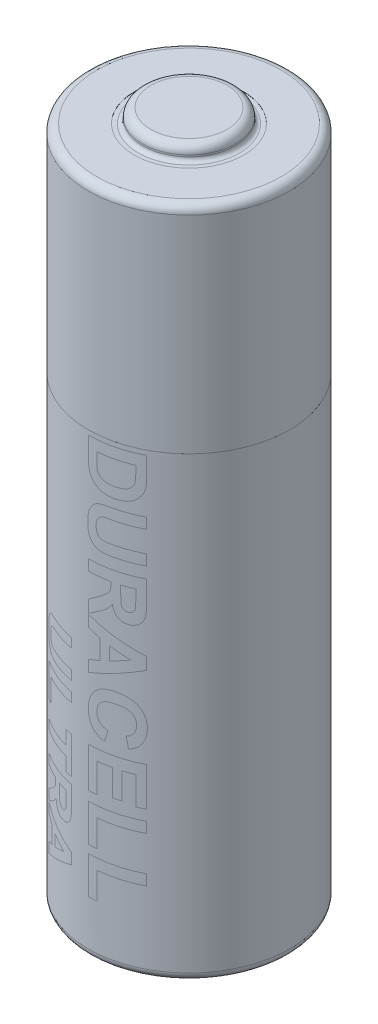
SolidWorks part; units mm, degrees
ref_plane "Front" through (0, 0, 0) normal (0, 0, 1) x (1, 0, 0)
ref_plane "Top" through (0, 0, 0) normal (0, 1, 0) x (1, 0, 0)
ref_plane "Right" through (0, 0, 0) normal (1, 0, 0) x (0, 0, -1)
sketch "Sketch1" plane through (0, 0, 0) normal (0, 0, 1) x (1, 0, 0)
  line L0 (0, 7.5818) -> (0, -7.5818) construction
  line L1 (0, 49.25) -> (0, -1)
  line L2 (3.95, 48.25) -> (3.95, 48.23)
  line L3 (6.65, 48.25) -> (3.95, 48.25)
  line L4 (7.25, 0.35) -> (7.25, 47.65)
  line L5 (0, 49.25) -> (2.75, 49.25)
  line L6 (6.2977, -0.25) -> (6.65, -0.25)
  line L7 (4.55, -0.24) -> (6.2977, -0.24)
  line L8 (3.35, 48.65) -> (3.35, 48.53)
  line L10 (3.65, 48.23) -> (3.95, 48.23)
  line L11 (0, -1) -> (3.95, -1)
  line L12 (4.25, -0.54) -> (4.25, -0.7)
  line L15 (6.2977, -0.24) -> (6.2977, -0.25)
  arc A0 (2.75, 49.25) -> (3.35, 48.65) centre (2.75, 48.65) cw
  arc A1 (3.95, -1) -> (4.25, -0.7) centre (3.95, -0.7) ccw
  arc A2 (6.65, 48.25) -> (7.25, 47.65) centre (6.65, 47.65) cw
  arc A3 (6.65, -0.25) -> (7.25, 0.35) centre (6.65, 0.35) ccw
  arc A4 (3.65, 48.23) -> (3.35, 48.53) centre (3.65, 48.53) cw
  arc A5 (4.25, -0.54) -> (4.55, -0.24) centre (4.55, -0.54) cw
  point P5 (3.35, 49.25)
  point P11 (4.25, -1)
  point P15 (7.25, 48.25)
  point P21 (7.25, -0.25)
  point P25 (3.35, 48.25)
  point P28 (4.25, -0.25)
  dimension "D1" = 0.6
  dimension "D8" = 0.3
  dimension "D9" = 0.6
  dimension "D10" = 0.3
  dimension "D11" = 0.3
  dimension "D2" = 7.25
  dimension "D3" = 48.5
  dimension "D4" = 0.75
  dimension "D5" = 1
  dimension "D6" = 2.75
  dimension "D7" = 4.25
revolve "Revolve1" add sketch "Sketch1" angle 360 about L0
ref_plane "Plane1" through (0, 0.35, 0) normal (0, -1, 0) x (1, 0, 0)
sketch "Sketch4" plane through (0, 0.35, 0) normal (0, -1, 0) x (1, 0, 0)
  circle A2 centre (0, 0) radius 7.2505
  circle A4 centre (0, 0) radius 6.2977
  dimension "D1" = 12.5954
  dimension "D2" = 14.501
extrude "Extrude3" add sketch "Sketch4" against normal blind 32.4
ref_plane "Plane2" through (0, 0, 7.25) normal (0, 0, 1) x (1, 0, 0)
sketch "Sketch5" plane through (0, 0, 7.25) normal (0, 0, 1) x (1, 0, 0)
  line L0 (0, 0) -> (0, 32.8291) construction
  text T0 "<b>DURACELL</b>" font "Arial" height 3.5
wrap "DURACELL" sketch "Sketch5" wrap type scribe source sketch "Sketch5" face at (0, 32.75, -7.2505)
sketch "Sketch6" plane through (0, 0, 7.25) normal (0, 0, 1) x (1, 0, 0)
  line L0 (-4.4268, 3.7211) -> (-4.4268, 23.1929) construction
  text T0 "<b>ULTRA</b>" font "Arial" height in points 12
wrap "ULTRA" sketch "Sketch6" wrap type scribe source sketch "Sketch6" face at (1.8548, 27.1534, 6.922)
